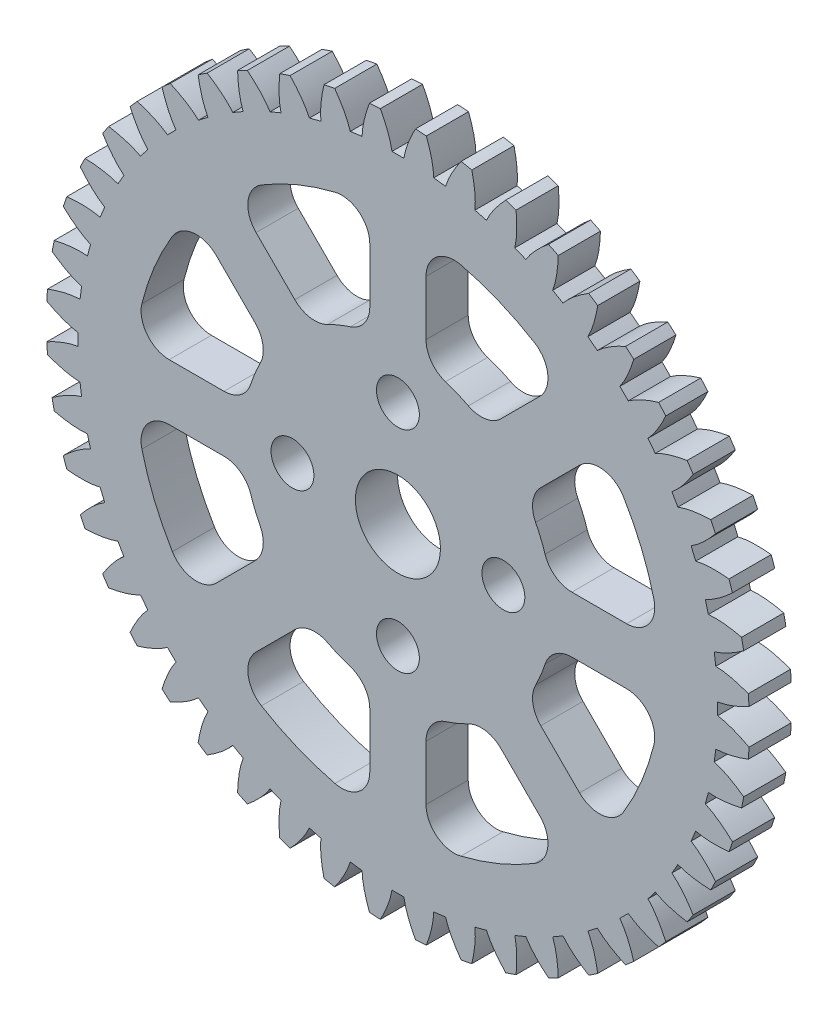
SolidWorks part; units mm, degrees
ref_plane "正面" through (0, 0, 0) normal (0, 0, 1) x (1, 0, 0)
ref_plane "平面" through (0, 0, 0) normal (0, 1, 0) x (1, 0, 0)
ref_plane "右側面" through (0, 0, 0) normal (1, 0, 0) x (0, 0, -1)
sketch "インボリュート スケッチ" plane through (0, 0, 0) normal (0, 0, 1) x (1, 0, 0)
  line L0 (-70.438, -23.8116) -> (0.4019, -22.549)
  line L1 (0.4019, -22.549) -> (-0.4019, 22.549) construction
  line L2 (0, 0) -> (0, 25) construction
  line L3 (-0.4019, 22.549) -> (-0.4054, 22.7464)
  line L4 (0, 0) -> (0.4019, -22.549)
  line L5 (-0.4054, 22.7464) -> (0, 22.7464)
  line L6 (0, 22.7464) -> (0, 0)
  circle A0 centre (0, 0) radius 22.5526 construction
  circle A1 centre (0, 0) radius 24 construction
  circle A2 centre (0, 0) radius 22.75 construction
  circle A3 centre (0, 0) radius 25 construction
  spline S0 degree 4 poles (-0.4019, 22.549) (-0.4043, 22.5919) (-0.4117, 22.6773) (-0.4369, 22.8471) (-0.4886, 23.0907) (-0.5628, 23.3644) (-0.6857, 23.7403) (-0.8782, 24.2318) (-1.1643, 24.8362) (-1.7417, 25.8497) (-2.6976, 27.1657) (-4.2523, 28.8251) (-6.5458, 30.6346) (-9.3246, 32.2398) (-12.5284, 33.5394) (-15.8665, 34.4327) (-19.283, 34.9432) (-22.9038, 35.1011) (-27.3837, 34.8283) (-32.6484, 33.82) (-38.5314, 31.7675) (-44.6351, 28.5052) (-49.5077, 24.9143) (-53.305, 21.3911) (-56.2012, 18.1959) (-58.352, 15.4987) (-60.3327, 12.6742) (-62.1401, 9.736) (-64.1797, 5.937) (-66.2726, 1.201) (-68.1932, -4.5312) (-69.3975, -10.0129) (-69.994, -14.2845) (-70.2598, -17.2892) (-70.355, -18.796) (-70.4098, -20.0849) (-70.4357, -21.0902) (-70.4466, -21.788) (-70.4498, -22.439) (-70.4494, -22.9528) (-70.4419, -23.6308) (-70.4328, -24.115) (-70.4123, -24.9069) (-70.3877, -25.5185) (-70.3541, -26.2633) (-70.3151, -26.928) (-70.2685, -27.6393) (-70.2157, -28.3236) (-70.1411, -29.1948) (-70.0385, -30.23) (-69.8993, -31.4416) (-69.7141, -32.8188) (-69.5557, -33.8513) (-69.4415, -34.5368) (-69.3823, -34.8798) knots 0 0 0 0 0 0.001401 0.002802 0.005604 0.008133 0.010661 0.015718 0.022839 0.02996 0.048734 0.068727 0.096889 0.125051 0.153212 0.181374 0.209535 0.237696 0.271429 0.327752 0.384075 0.440398 0.496721 0.524883 0.553044 0.581206 0.609367 0.637529 0.66569 0.722013 0.778336 0.834659 0.84874 0.86282 0.876901 0.883942 0.890982 0.895509 0.900036 0.904564 0.909091 0.914773 0.920455 0.926136 0.931818 0.9375 0.943182 0.948864 0.954545 0.965909 0.977273 0.988636 1 1 1 1 1 construction
  spline S1 degree 4 poles (-0.4019, 22.549) (-0.4043, 22.5919) (-0.4117, 22.6773) (-0.4369, 22.8471) (-0.4886, 23.0907) (-0.5628, 23.3644) (-0.6857, 23.7403) (-0.8782, 24.2318) (-1.1643, 24.8362) (-1.7417, 25.8497) (-2.6976, 27.1657) (-4.2523, 28.8251) (-6.5458, 30.6346) (-9.3246, 32.2398) (-12.5284, 33.5394) (-15.8665, 34.4327) (-19.283, 34.9432) (-22.9038, 35.1011) (-27.3837, 34.8283) (-32.6484, 33.82) (-38.5314, 31.7675) (-44.6351, 28.5052) (-49.5077, 24.9143) (-53.305, 21.3911) (-56.2012, 18.1959) (-58.352, 15.4987) (-60.3327, 12.6742) (-62.1401, 9.736) (-64.1797, 5.937) (-66.2726, 1.201) (-68.1932, -4.5312) (-69.3975, -10.0129) (-69.994, -14.2845) (-70.2598, -17.2892) (-70.355, -18.796) (-70.4098, -20.0849) (-70.4357, -21.0902) (-70.4466, -21.788) (-70.4498, -22.439) (-70.4494, -22.9528) (-70.4441, -23.4308) (-70.4403, -23.6856) (-70.438, -23.8116) knots 0 0 0 0 0 0.001401 0.002802 0.005604 0.008133 0.010661 0.015718 0.022839 0.02996 0.048734 0.068727 0.096889 0.125051 0.153212 0.181374 0.209535 0.237696 0.271429 0.327752 0.384075 0.440398 0.496721 0.524883 0.553044 0.581206 0.609367 0.637529 0.66569 0.722013 0.778336 0.834659 0.84874 0.86282 0.876901 0.883942 0.890982 0.895509 0.900036 0.904564 0.909091 0.909091 0.909091 0.909091 0.909091
  point P6 (-0.7853, 23.9872)
  point P12 (0, 24)
  point P24 (0, 0)
  dimension "D1" = 45.1052
  dimension "D2" = 48
  dimension "D3" = 45.5
  dimension "D4" = 50
  dimension "D5" = 0.7854
extrude "インボリュート ボス" add sketch "インボリュート スケッチ" along normal blind 3 contours S1 L0 L4 region at (-31.7048, 2.4995, 0)
mirror "インボリュート ミラー" about plane through (0, 0, 3) normal (1, 0, 0) of bodies 161
sketch "歯先円 スケッチ" plane through (0, 0, 3) normal (0, 0, 1) x (1, 0, 0)
  circle A0 centre (0, 0) radius 74.3539
  circle A1 centre (0, 0) radius 25
  dimension "D1" = 50
extrude "歯先円 カット" cut sketch "歯先円 スケッチ" against normal through all
sketch "歯分割 スケッチ" plane through (0, 0, 3) normal (0, 0, 1) x (1, 0, 0)
  line L0 (-1.6351, 24.9465) -> (0, 0)
  line L1 (0, 0) -> (1.6351, 24.9465)
  line L2 (0, 0) -> (0, 24) construction
  arc A0 (-1.6351, 24.9465) -> (1.6351, 24.9465) centre (0, 0) ccw
  circle A2 centre (0, 0) radius 24 construction
  arc A3 (-1.2492, 24.9688) -> (-10.3843, -22.7413) centre (0, 0) ccw construction
  point P9 (-1.5697, 23.9486)
  point P10 (1.5697, 23.9486)
  dimension "D1" = 48
  dimension "D2" = 3.1416
extrude "歯分割 カット" cut sketch "歯分割 スケッチ" against normal through all
pattern_circular "歯分割 円形コピー" count 48 over 360 about axis through (0, 0, 0) along (0, 0, 1) of bodies 166
sketch "歯底円 スケッチ" plane through (0, 0, 3) normal (0, 0, 1) x (1, 0, 0)
  circle A0 centre (0, 0) radius 22.75
  dimension "D1" = 45.5
extrude "歯底円 ボス" add sketch "歯底円 スケッチ" against normal through all
sketch "軸 丸穴 スケッチ" plane through (0, 0, 3) normal (0, 0, 1) x (1, 0, 0)
  circle A0 centre (0, 0) radius 3.025
  dimension "D1" = 6.05
extrude "軸 丸穴 カット" cut sketch "軸 丸穴 スケッチ" against normal through all
sketch "軸 キー溝 スケッチ" plane through (0, 0, 3) normal (0, 0, 1) x (1, 0, 0)
  line L2 (-1.5, 3.7081) -> (-1.5, 5.4)
  line L3 (-1.5, 5.4) -> (1.5, 5.4)
  line L4 (1.5, 3.7081) -> (1.5, 5.4)
  arc A0 (-1.5, 3.7081) -> (1.5, 3.7081) centre (0, 0) ccw
  dimension "D1" = 8
  dimension "D2" = 3
  dimension "D3" = 5.4
extrude "軸 キー溝 カット" [suppressed] cut sketch "軸 キー溝 スケッチ" against normal through all
sketch "軸 Dカット スケッチ" plane through (0, 0, 3) normal (0, 0, 1) x (1, 0, 0)
  line L0 (-2.3958, 3) -> (2.3958, 3)
  arc A0 (-2.828, 2.8289) -> (2.828, 2.8289) centre (0, 0) ccw
  arc A1 (-2.3958, 3) -> (-2.828, 2.8289) centre (-2.6458, 3) ccw
  arc A2 (2.828, 2.8289) -> (2.3958, 3) centre (2.6458, 3) ccw
  dimension "D1" = 8
  dimension "D3" = 0.5
  dimension "D2" = 3
extrude "軸 Dカット カット" [suppressed] cut sketch "軸 Dカット スケッチ" against normal through all
sketch "軸 角穴 スケッチ" plane through (0, 0, 3) normal (0, 0, 1) x (1, 0, 0)
  line L0 (-5.1, 5.1) -> (5.1, 5.1)
  line L1 (-5, -5) -> (5, -5) construction
  line L2 (-5, -5) -> (-5, 5) construction
  line L3 (-5, 5) -> (5, 5) construction
  line L4 (5, -5) -> (5, 5) construction
  line L5 (-5, -5) -> (5, 5) construction
  line L6 (-5, 5) -> (5, -5) construction
  line L7 (5.1, -5.1) -> (5.1, 5.1)
  line L8 (-5.1, -5.1) -> (5.1, -5.1)
  line L9 (-5.1, -5.1) -> (-5.1, 5.1)
  point P0 (0, 0)
  dimension "D1" = 10
  dimension "D2" = 0.1
extrude "軸 角穴 カット" [suppressed] cut sketch "軸 角穴 スケッチ" against normal through all
sketch "フランジ穴 スケッチ" plane through (0, 0, 3) normal (0, 0, 1) x (1, 0, 0)
  circle A0 centre (0, 12) radius 1.6
  circle A1 centre (12, 0) radius 1.6
  circle A2 centre (0, -12) radius 1.6
  circle A3 centre (-12, 0) radius 1.6
  point P12 (0, 0)
  dimension "D2" = 3.2
  dimension "D3" = 12
  dimension "D1" = 4
extrude "フランジ穴 カット" [suppressed] cut sketch "フランジ穴 スケッチ" against normal through all
sketch "合致用スケッチ" plane through (0, 0, 3) normal (0, 0, 1) x (1, 0, 0)
  line L0 (0, 0) -> (0, 24)
  line L1 (0, 0) -> (1.5697, 23.9486)
  circle A2 centre (0, 0) radius 24
  dimension "D1" = 48
  dimension "D2" = 3.75
sketch "ｽｹｯﾁ1" plane through (0, 0, 0) normal (0, 0, -1) x (-1, 0, 0)
  line L0 (0, 0) -> (0, 24) construction
  circle A0 centre (0, 7.5) radius 1.525
  circle A1 centre (7.5, 0) radius 1.525
  circle A2 centre (0, -7.5) radius 1.525
  circle A3 centre (-7.5, 0) radius 1.525
  point P14 (0, 0)
  dimension "D1" = 7.5
  dimension "D2" = 3.05
  dimension "D3" = 4
extrude "ｶｯﾄ - 押し出し1" cut sketch "ｽｹｯﾁ1" against normal through all
chamfer "面取り1" [suppressed] distance 1.75 angle 45
sketch "ｽｹｯﾁ2" plane through (0, 0, 3) normal (0, 0, 1) x (1, 0, 0)
  line L0 (0, 0) -> (0, -22.7464) construction
  line L1 (-0.4054, -22.7464) -> (0.4054, -22.7464) construction
  line L2 (0, 0) -> (-16.0841, -16.0841) construction
  line L3 (0, 0) -> (-22.7464, 0) construction
  line L4 (0, 0) -> (-16.0841, 16.0841) construction
  line L5 (0, 0) -> (0, 22.7464) construction
  line L6 (0, 0) -> (16.0841, 16.0841) construction
  line L7 (0, 0) -> (22.7464, 0) construction
  line L8 (0, 0) -> (16.0841, -16.0841) construction
  line L9 (-6.2343, -9.0627) -> (-11.7684, -14.5968)
  line L10 (-2, -18.643) -> (-2, -10.8167)
  line L11 (-14.5968, -11.7684) -> (-9.0627, -6.2343)
  line L12 (-10.8167, -2) -> (-18.643, -2)
  line L13 (-18.643, 2) -> (-10.8167, 2)
  line L14 (-9.0627, 6.2343) -> (-14.5968, 11.7684)
  line L15 (-11.7684, 14.5968) -> (-6.2343, 9.0627)
  line L16 (-2, 10.8167) -> (-2, 18.643)
  line L17 (2, 18.643) -> (2, 10.8167)
  line L18 (6.2343, 9.0627) -> (11.7684, 14.5968)
  line L19 (14.5968, 11.7684) -> (9.0627, 6.2343)
  line L20 (10.8167, 2) -> (18.643, 2)
  line L21 (18.643, -2) -> (10.8167, -2)
  line L22 (9.0627, -6.2343) -> (14.5968, -11.7684)
  line L23 (11.7684, -14.5968) -> (6.2343, -9.0627)
  line L24 (2, -10.8167) -> (2, -18.643)
  arc A0 (-2, -10.8167) -> (-6.2343, -9.0627) centre (0, 0) cw
  arc A1 (-2, -18.643) -> (-11.7684, -14.5968) centre (0, 0) cw
  arc A2 (-9.0627, -6.2343) -> (-10.8167, -2) centre (0, 0) cw
  arc A3 (-14.5968, -11.7684) -> (-18.643, -2) centre (0, 0) cw
  arc A4 (-10.8167, 2) -> (-9.0627, 6.2343) centre (0, 0) cw
  arc A5 (-18.643, 2) -> (-14.5968, 11.7684) centre (0, 0) cw
  arc A6 (-6.2343, 9.0627) -> (-2, 10.8167) centre (0, 0) cw
  arc A7 (-11.7684, 14.5968) -> (-2, 18.643) centre (0, 0) cw
  arc A8 (2, 10.8167) -> (6.2343, 9.0627) centre (0, 0) cw
  arc A9 (2, 18.643) -> (11.7684, 14.5968) centre (0, 0) cw
  arc A10 (9.0627, 6.2343) -> (10.8167, 2) centre (0, 0) cw
  arc A11 (14.5968, 11.7684) -> (18.643, 2) centre (0, 0) cw
  arc A12 (10.8167, -2) -> (9.0627, -6.2343) centre (0, 0) cw
  arc A13 (18.643, -2) -> (14.5968, -11.7684) centre (0, 0) cw
  arc A14 (6.2343, -9.0627) -> (2, -10.8167) centre (0, 0) cw
  arc A15 (11.7684, -14.5968) -> (2, -18.643) centre (0, 0) cw
  point P14 (0, 0)
  point P47 (0, 0)
  dimension "D2" = 11
  dimension "D3" = 18.75
  dimension "D4" = 2
  dimension "D5" = 2
  dimension "D1" = 8
  dimension "D6" = 8
extrude "ｶｯﾄ - 押し出し2" cut sketch "ｽｹｯﾁ2" against normal through all
fillet "ﾌｨﾚｯﾄ1" radius 2 32 edges at (-2, -18.643, 1.5) (-11.7684, -14.5968, 1.5) (-6.2343, -9.0627, 1.5) (-2, -10.8167, 1.5) (14.5968, 11.7684, 1.5) (18.643, 2, 1.5) (10.8167, 2, 1.5) (9.0627, 6.2343, 1.5) (18.643, -2, 1.5) (14.5968, -11.7684, 1.5) (9.0627, -6.2343, 1.5) (10.8167, -2, 1.5) (11.7684, -14.5968, 1.5) (2, -18.643, 1.5) (2, -10.8167, 1.5) (6.2343, -9.0627, 1.5) (-14.5968, -11.7684, 1.5) (-18.643, -2, 1.5) (-10.8167, -2, 1.5) (-9.0627, -6.2343, 1.5) (-18.643, 2, 1.5) (-14.5968, 11.7684, 1.5) (-9.0627, 6.2343, 1.5) (-10.8167, 2, 1.5) (-11.7684, 14.5968, 1.5) (-2, 10.8167, 1.5) (-6.2343, 9.0627, 1.5) (2, 18.643, 1.5) (11.7684, 14.5968, 1.5) (6.2343, 9.0627, 1.5) (2, 10.8167, 1.5) (-2, 18.643, 1.5)
equation "\"モジュール\"= 1."
equation "\"基準圧力角\"= 20"
equation "\"歯数\"= 48"
equation "\"基準円直径\"= \"歯数\" * \"モジュール\""
equation "\"基礎円直径\"= \"基準円直径\" * cos ( \"基準圧力角\" )"
equation "\"歯先円直径\"= \"基準円直径\" + 2 * \"モジュール\""
equation "\"歯底円直径\"= \"基準円直径\" - 2.5 * \"モジュール\""
equation "\"D1@インボリュート スケッチ\" = \"基礎円直径\""
equation "\"D2@インボリュート スケッチ\" = \"基準円直径\""
equation "\"D3@インボリュート スケッチ\" = \"歯底円直径\""
equation "\"D4@インボリュート スケッチ\" = \"歯先円直径\""
equation "\"D5@インボリュート スケッチ\" = Pi * \"モジュール\" / 4"
equation "\"D1@歯先円 スケッチ\" = \"歯先円直径\""
equation "\"D1@歯分割 スケッチ\" = \"基準円直径\""
equation "\"D2@歯分割 スケッチ\" = PI * \"モジュール\""
equation "\"D1@歯分割 円形コピー\" = \"歯数\""
equation "\"D1@歯底円 スケッチ\" = \"歯底円直径\""
equation "\"板厚\"= 3"
equation "\"D1@インボリュート ボス\"=\"板厚\""
equation "\"D1@合致用スケッチ\" = \"基準円直径\""
equation "\"D2@合致用スケッチ\"=180/\"歯数\""
